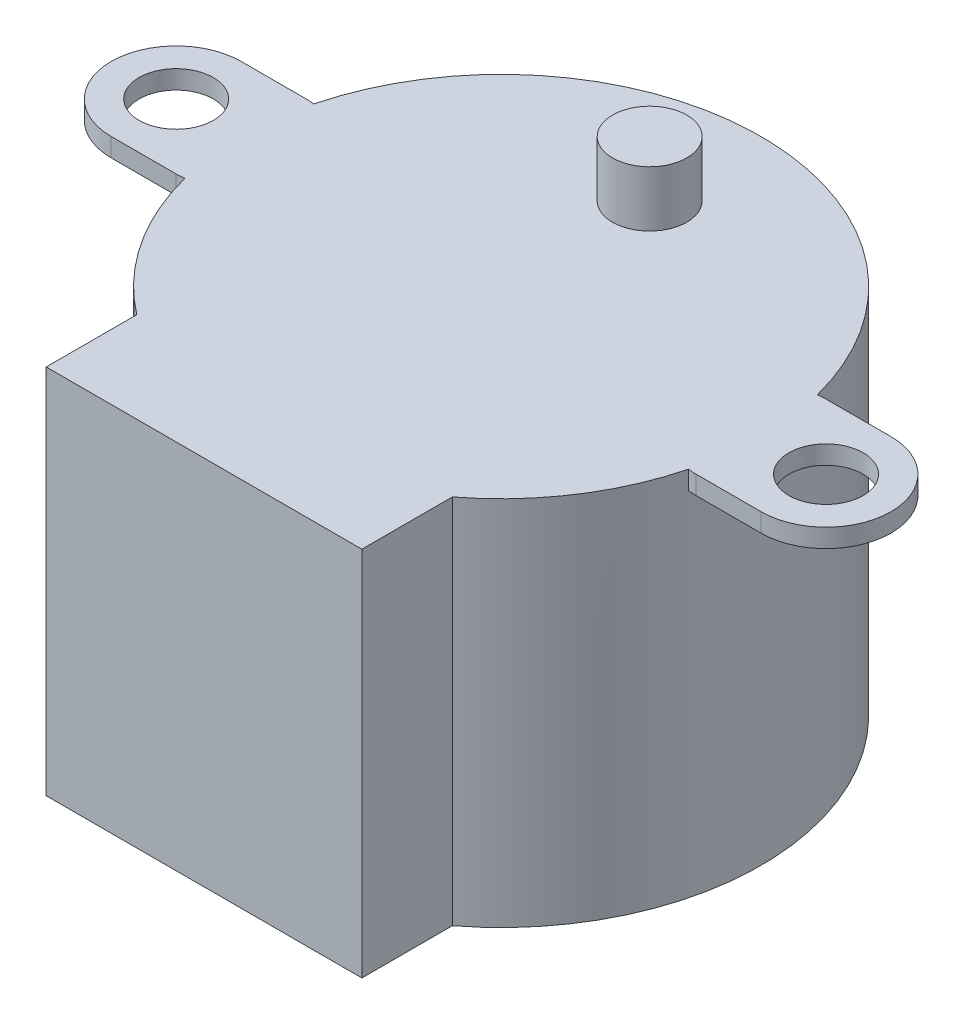
SolidWorks part; units mm, degrees
ref_plane "Front Plane" through (0, 0, 0) normal (0, 0, 1) x (1, 0, 0)
ref_plane "Top Plane" through (0, 0, 0) normal (0, 1, 0) x (1, 0, 0)
ref_plane "Right Plane" through (0, 0, 0) normal (1, 0, 0) x (0, 0, -1)
sketch "Sketch1" plane through (0, 0, 0) normal (0, 1, 0) x (1, 0, 0)
  line L1 (-8.5, -11.1243) -> (8.5, -11.1243)
  line L2 (-8.5, -11.1243) -> (-8.5, -16)
  line L3 (-8.5, -16) -> (8.5, -16)
  line L4 (8.5, -11.1243) -> (8.5, -16)
  circle A0 centre (0, 0) radius 14
  point P8 (0, -14)
  dimension "D1" = 28
  dimension "D2" = 17
  dimension "D3" = 2
extrude "Boss-Extrude1" add sketch "Sketch1" along normal blind 20 contours L1 A0 | A0 L2 L3 L4 | L1 A0 region at (0, 0, -0.7029) region at (0, 0, 14.4207) region at (0, 0, 12.2853)
sketch "Sketch2" plane through (0, 20, 0) normal (0, 1, 0) x (1, 0, 0)
  line L0 (-14, 0) -> (14, 0) construction
  line L1 (14, 0) -> (17.5, 0) construction
  line L2 (14, 3.5) -> (17.5, 3.5)
  line L3 (14, -3.5) -> (17.5, -3.5)
  line L4 (0, 0) -> (0, 14) construction
  line L5 (-14, 0) -> (-17.5, 0) construction
  line L6 (-14, 3.5) -> (-17.5, 3.5)
  line L7 (-14, -3.5) -> (-17.5, -3.5)
  arc A0 (8.5, -11.1243) -> (-8.5, -11.1243) centre (0, 0) ccw construction
  arc A1 (14, 3.5) -> (14, -3.5) centre (14, 0) ccw
  arc A2 (17.5, -3.5) -> (17.5, 3.5) centre (17.5, 0) ccw
  circle A3 centre (17.5, 0) radius 2
  circle A4 centre (-17.5, 0) radius 2
  arc A5 (-14, 3.5) -> (-14, -3.5) centre (-14, 0) cw
  arc A6 (-17.5, -3.5) -> (-17.5, 3.5) centre (-17.5, 0) cw
  point P6 (15.75, 0)
  point P19 (-15.75, 0)
  dimension "D2" = 3.5
  dimension "D3" = 4
  dimension "D1" = 3.5
extrude "Boss-Extrude2" add sketch "Sketch2" against normal blind 1
sketch "Sketch3" plane through (0, 20, 0) normal (0, 1, 0) x (1, 0, 0)
  line L0 (0, 0) -> (0, 14) construction
  arc A0 (13.5625, 3.4725) -> (-13.5625, 3.4725) centre (0, 0) ccw construction
  circle A1 centre (0, 8) radius 2
  dimension "D1" = 6
extrude "Boss-Extrude3" add sketch "Sketch3" along normal blind 3
